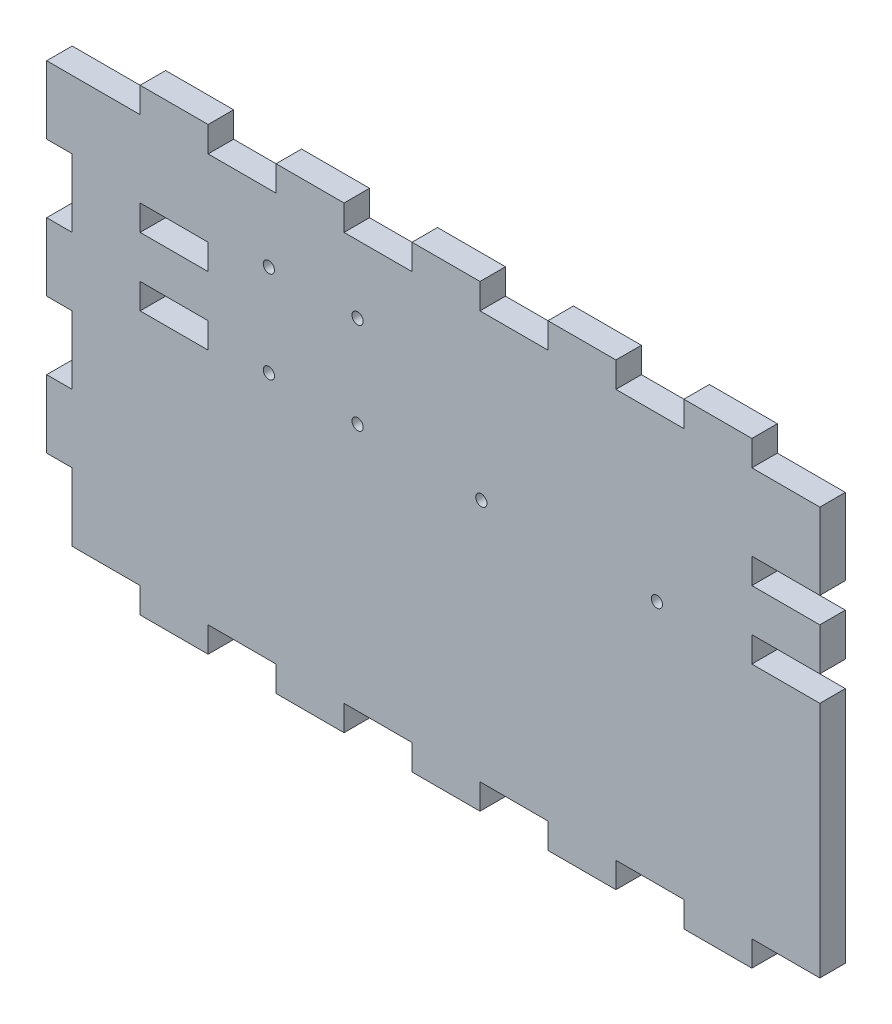
SolidWorks part; units mm, degrees
ref_plane "Front Plane" through (0, 0, 0) normal (0, 0, 1) x (1, 0, 0)
ref_plane "Top Plane" through (0, 0, 0) normal (0, 1, 0) x (1, 0, 0)
ref_plane "Right Plane" through (0, 0, 0) normal (1, 0, 0) x (0, 0, -1)
sketch "Sketch1" plane through (0, 0, 0) normal (0, 0, 1) x (1, 0, 0)
  line L1 (-139.7, -76.2) -> (139.7, -76.2)
  line L2 (-139.7, -76.2) -> (-139.7, 76.2)
  line L3 (-139.7, 76.2) -> (139.7, 76.2)
  line L4 (139.7, -76.2) -> (139.7, 76.2)
  line L5 (-139.7, -76.2) -> (139.7, 76.2) construction
  line L6 (-139.7, 76.2) -> (139.7, -76.2) construction
  point P0 (0, 0)
  dimension "D1" = 279.4
  dimension "D2" = 152.4
extrude "Boss-Extrude1" add sketch "Sketch1" along normal blind 9.525
sketch "Sketch2" plane through (0, -76.2, 0) normal (0, -1, 0) x (1, 0, 0)
  line L0 (-139.7, 0) -> (139.7, 0) construction
  line L1 (-114.3, 0) -> (-88.9, 0)
  line L2 (-114.3, 0) -> (-114.3, 9.525)
  line L3 (-114.3, 9.525) -> (-88.9, 9.525)
  line L4 (-88.9, 0) -> (-88.9, 9.525)
  line L5 (-139.7, 9.525) -> (139.7, 9.525) construction
  line L6 (-139.7, 9.525) -> (-139.7, 0) construction
  point P10 (-139.7, 4.7625)
  dimension "D1" = 25.4
  dimension "D2" = 25.4
extrude "Boss-Extrude2" add sketch "Sketch2" along normal blind 9.525
pattern_linear "LPattern1" count 5 spacing 50.8 along (1, 0, 0) of "Boss-Extrude2"
mirror "Mirror1" about plane through (0, 0, 0) normal (0, 1, 0) of "LPattern1"
sketch "Sketch3" plane through (-139.7, 0, 0) normal (-1, 0, 0) x (0, 0, 1)
  line L0 (0, 76.2) -> (0, -76.2) construction
  line L1 (9.525, 76.2) -> (0, 76.2)
  line L2 (9.525, 76.2) -> (9.525, 50.8)
  line L3 (9.525, 50.8) -> (0, 50.8)
  line L4 (0, 76.2) -> (0, 50.8)
  dimension "D1" = 25.4
extrude "Boss-Extrude3" add sketch "Sketch3" along normal blind 9.525
pattern_linear "LPattern2" count 3 spacing 50.8 along (0, -1, 0) of "Boss-Extrude3"
sketch "Sketch4" plane through (0, 0, 0) normal (0, 0, -1) x (-1, 0, 0)
  line L1 (-139.7, 12.7) -> (-114.3, 12.7)
  line L2 (-139.7, 12.7) -> (-139.7, 22.225)
  line L3 (-139.7, 22.225) -> (-114.3, 22.225)
  line L4 (-114.3, 12.7) -> (-114.3, 22.225)
  line L5 (-114.3, -76.2) -> (-139.7, -76.2) construction
  line L6 (-139.7, -76.2) -> (-139.7, 76.2) construction
  dimension "D1" = 25.4
  dimension "D2" = 9.525
  dimension "D4" = 88.9
extrude "Cut-Extrude1" cut sketch "Sketch4" against normal through all
pattern_linear "LPattern3" count 2 spacing 228.6 along (-1, 0, 0) of "Cut-Extrude1"
sketch "Sketch5" plane through (0, 0, 9.525) normal (0, 0, 1) x (1, 0, 0)
  line L1 (-88.9, 47.625) -> (-114.3, 47.625)
  line L2 (-88.9, 47.625) -> (-88.9, 38.1)
  line L3 (-88.9, 38.1) -> (-114.3, 38.1)
  line L4 (-114.3, 47.625) -> (-114.3, 38.1)
  line L5 (-88.9, -76.2) -> (-63.5, -76.2) construction
  line L8 (-114.3, 12.7) -> (-114.3, 22.225) construction
  dimension "D1" = 25.4
  dimension "D2" = 9.525
  dimension "D3" = 114.3
extrude "Cut-Extrude2" cut sketch "Sketch5" against normal through all
pattern_linear "LPattern4" count 2 spacing 228.6 along (1, 0, 0) of "Cut-Extrude2"
sketch "Sketch6" plane through (0, 0, 0) normal (0, 0, -1) x (-1, 0, 0)
  circle A0 centre (-78.8111, 15.175) radius 2.1 construction
  circle A1 centre (-78.8111, 15.175) radius 2.1
  circle A2 centre (-13.2039, 15.175) radius 2.1 construction
  circle A3 centre (-13.2039, 15.175) radius 2.1
  circle A4 centre (66.195, 16.6838) radius 2.1 construction
  circle A5 centre (66.195, 16.6838) radius 2.1
  circle A6 centre (33.045, 50.945) radius 2.1 construction
  circle A7 centre (33.045, 50.945) radius 2.1
  circle A8 centre (66.195, 50.945) radius 2.1 construction
  circle A9 centre (66.195, 50.945) radius 2.1
  circle A10 centre (33.045, 16.6838) radius 2.1 construction
  circle A11 centre (33.045, 16.6838) radius 2.1
extrude "Cut-Extrude3" cut sketch "Sketch6" against normal through all
